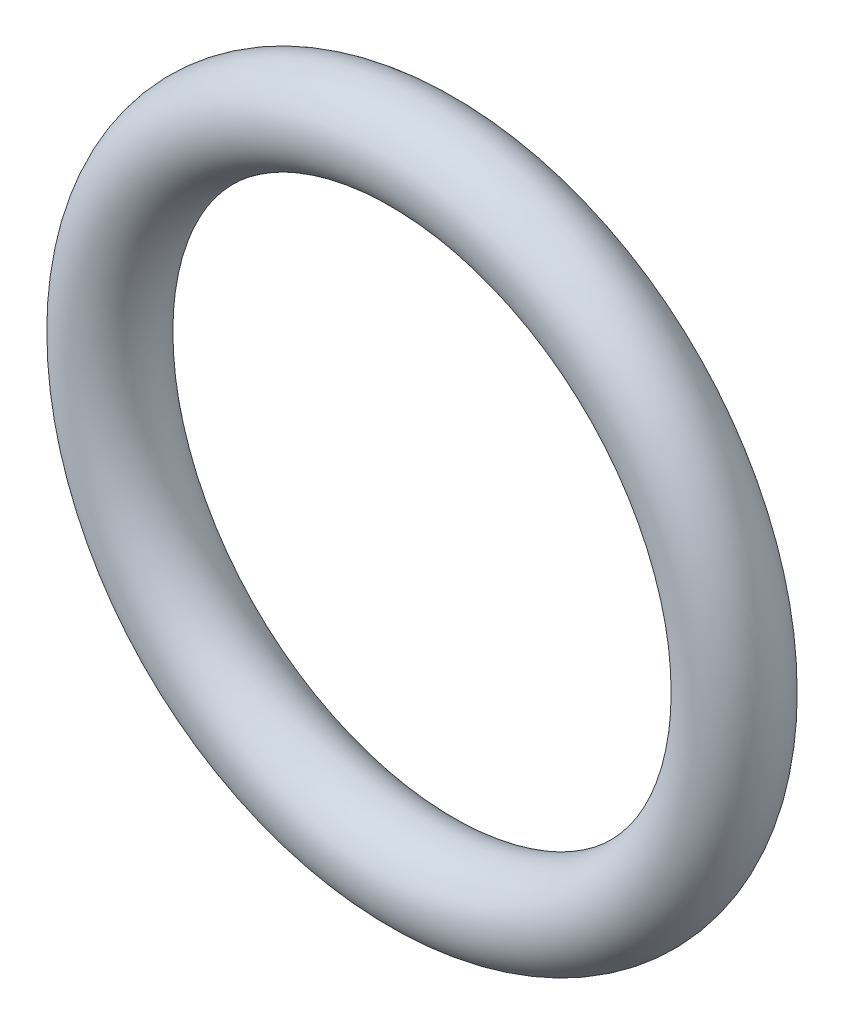
SolidWorks part; units mm, degrees
ref_plane "Спереди" through (0, 0, 0) normal (0, 0, 1) x (1, 0, 0)
ref_plane "Сверху" through (0, 0, 0) normal (0, 1, 0) x (1, 0, 0)
ref_plane "Справа" through (0, 0, 0) normal (1, 0, 0) x (0, 0, -1)
sketch "Эскиз1" plane through (0, 0, 0) normal (1, 0, 0) x (0, 0, -1)
  line L0 (0, 0) -> (0, 3.5) construction
  line L1 (1.317, 0) -> (-1.2055, 0) construction
  circle A0 centre (0, 3.5) radius 0.5
revolve "Повернуть2" add sketch "Эскиз1" angle 360 about L1 region at (0, 3.5, 0)
sketch "Эскиз2" plane through (0, 0, 0) normal (1, 0, 0) x (0, 0, -1)
  line L0 (0, 0) -> (-8.82, 0) construction
ref_axis "Ось1" through (0, 0, 0) along (0, 0, 1)
